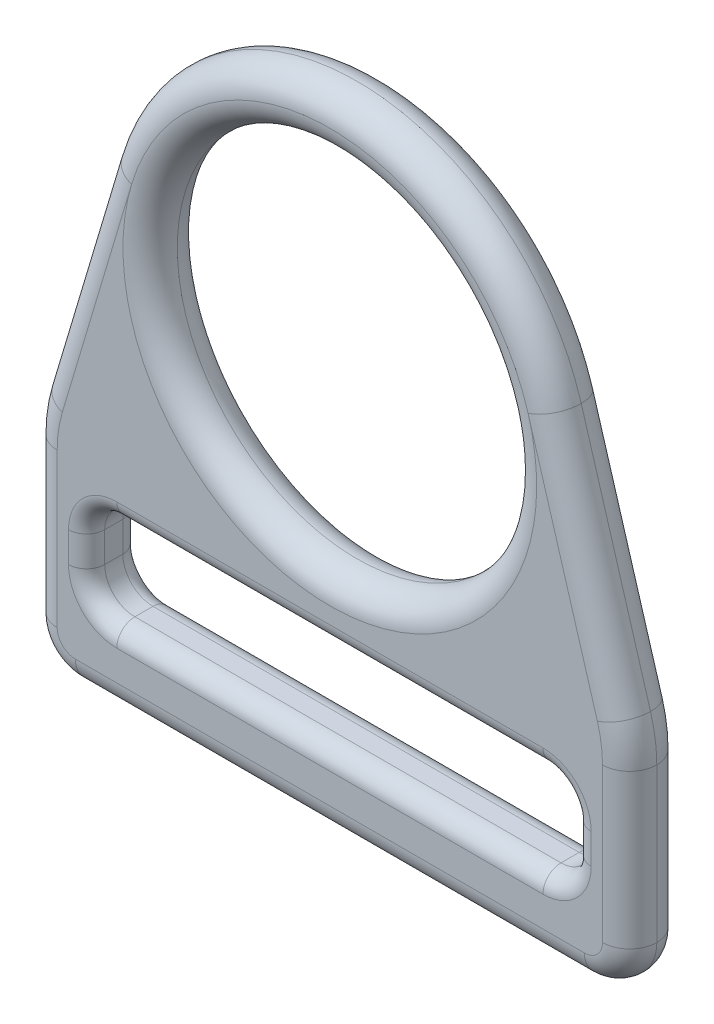
SolidWorks part; units mm, degrees
ref_plane "Front Plane" through (0, 0, 0) normal (0, 0, 1) x (1, 0, 0)
ref_plane "Top Plane" through (0, 0, 0) normal (0, 1, 0) x (1, 0, 0)
ref_plane "Right Plane" through (0, 0, 0) normal (1, 0, 0) x (0, 0, -1)
sketch "Sketch2" plane through (0, 0, 0) normal (1, 0, 0) x (0, 0, -1)
  circle A0 centre (0, 0) radius 2.286
  dimension "D1" = 4.572
sketch "Sketch3" plane through (0, 0, 0) normal (0, 0, 1) x (1, 0, 0)
  circle A0 centre (0, -17.4149) radius 17.4149
  point P3 (0, 0)
  dimension "D1" = 34.8297
sweep "Sweep1" add profiles "Sketch2" path "Sketch3"
sketch "Sketch4" plane through (0, 0, 0) normal (0, 0, 1) x (1, 0, 0)
  line L0 (-18.8772, -11.7778) -> (-24.7103, -31.3113)
  line L1 (-25.2413, -34.9452) -> (-25.2412, -47.8949)
  line L2 (-21.4312, -51.7049) -> (21.4313, -51.7049)
  line L3 (25.2413, -47.8949) -> (25.2413, -34.9452)
  line L4 (24.7103, -31.3113) -> (18.8772, -11.7778)
  line L5 (-20.4788, -40.2749) -> (-20.4787, -42.8149)
  line L6 (-17.9387, -45.3549) -> (17.9388, -45.3549)
  line L7 (20.4788, -42.8149) -> (20.4788, -40.2749)
  line L8 (17.9388, -37.7349) -> (-17.9387, -37.7349)
  line L9 (0, -17.4149) -> (0, -51.7049) construction
  arc A2 (21.4313, -51.7049) -> (25.2413, -47.8949) centre (21.4313, -47.8949) ccw
  arc A3 (-25.2412, -47.8949) -> (-21.4312, -51.7049) centre (-21.4312, -47.8949) ccw
  arc A4 (20.4788, -40.2749) -> (17.9388, -37.7349) centre (17.9388, -40.2749) ccw
  arc A5 (17.9388, -45.3549) -> (20.4788, -42.8149) centre (17.9388, -42.8149) ccw
  arc A6 (-20.4787, -42.8149) -> (-17.9387, -45.3549) centre (-17.9387, -42.8149) ccw
  arc A7 (-20.4788, -40.2749) -> (-17.9387, -37.7349) centre (-17.9387, -40.2749) cw
  arc A8 (25.2413, -34.9452) -> (24.7103, -31.3113) centre (12.5412, -34.9452) ccw
  arc A9 (-24.7103, -31.3113) -> (-25.2413, -34.9452) centre (-12.5412, -34.9452) ccw
  circle A10 centre (0, -17.4149) radius 19.7009 construction
  arc A11 (18.8772, -11.7778) -> (-18.8772, -11.7778) centre (0, -17.4149) ccw
  circle A12 centre (0, -17.4149) radius 15.1289 construction
  circle A13 centre (0, -17.4149) radius 15.1289
  point P6 (0, 0)
  point P26 (0, 0)
  point P30 (0, 2.286)
  dimension "D1" = 3.81
  dimension "D2" = 2.54
  dimension "D3" = 12.7
  dimension "D4" = 6.35
  dimension "D5" = 4.7625
  dimension "D6" = 42.8625
  dimension "D7" = 7.62
  dimension "D8" = 34.29
  dimension "D9" = 19.5335
extrude "Boss-Extrude1" add sketch "Sketch4" along normal through all and the other way through all
fillet "Fillet1" radius 2.286 22 edges at (21.7937, -21.5446, 2.286) (25.1078, -33.109, 2.286) (25.2413, -41.42, 2.286) (24.1253, -50.589, 2.286) (0, -51.7049, 2.286) (-24.1253, -50.589, 2.286) (-25.2412, -41.42, 2.286) (-25.1078, -33.109, 2.286) (-21.7937, -21.5446, 2.286) (21.7937, -21.5446, -2.286) (25.1078, -33.109, -2.286) (25.2413, -41.42, -2.286) (24.1253, -50.589, -2.286) (0, -51.7049, -2.286) (-24.1253, -50.589, -2.286) (-25.2412, -41.42, -2.286) (-25.1078, -33.109, -2.286) (-21.7937, -21.5446, -2.286) (15.1289, -17.4149, 2.286) (15.1289, -17.4149, -2.286) (0, 2.286, 2.286) (0, 2.286, -2.286)
fillet "Fillet2" radius 1.524 16 edges at (-19.7348, -44.6109, 2.286) (-20.4787, -41.5449, 2.286) (-19.7348, -38.4788, 2.286) (0, -37.7349, 2.286) (19.7348, -38.4788, 2.286) (20.4788, -41.5449, 2.286) (19.7348, -44.6109, 2.286) (-19.7348, -44.6109, -2.286) (-20.4787, -41.5449, -2.286) (-19.7348, -38.4788, -2.286) (0, -37.7349, -2.286) (19.7348, -38.4788, -2.286) (20.4788, -41.5449, -2.286) (19.7348, -44.6109, -2.286) (0, -45.3549, 2.286) (0, -45.3549, -2.286)
